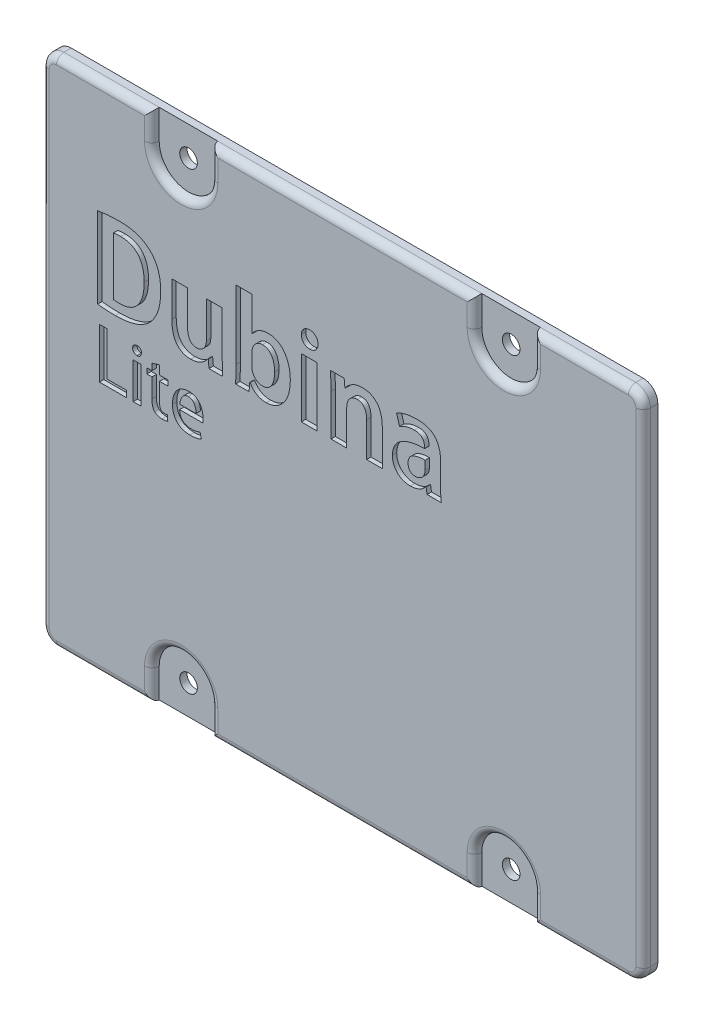
SolidWorks part; units mm, degrees
ref_plane "Спереди" through (0, 0, 0) normal (0, 0, 1) x (1, 0, 0)
ref_plane "Сверху" through (0, 0, 0) normal (0, 1, 0) x (1, 0, 0)
ref_plane "Справа" through (0, 0, 0) normal (1, 0, 0) x (0, 0, -1)
other "Configuration Table"
sketch "Эскиз2" plane through (0, 0, 0) normal (0, 0, 1) x (1, 0, 0)
  line L0 (-39, 35) -> (39, 35)
  line L1 (41, 33) -> (41, -33)
  line L2 (39, -35) -> (-39, -35)
  line L3 (-41, -33) -> (-41, 33)
  line L4 (-18, -31) -> (-18, -35)
  line L5 (-26, -31) -> (-26, -35)
  line L6 (26, -31) -> (26, -35)
  line L7 (18, -31) -> (18, -35)
  line L8 (26, 31) -> (26, 35)
  line L9 (18, 31) -> (18, 35)
  line L10 (-18, 31) -> (-18, 35)
  line L11 (-26, 31) -> (-26, 35)
  arc A0 (-39, 35) -> (-41, 33) centre (-39, 33) ccw construction
  arc A1 (41, 33) -> (39, 35) centre (39, 33) ccw construction
  arc A2 (39, -35) -> (41, -33) centre (39, -33) ccw construction
  arc A3 (-41, -33) -> (-39, -35) centre (-39, -33) ccw construction
  arc A4 (-39, 35) -> (-41, 33) centre (-39, 33) ccw
  arc A5 (41, 33) -> (39, 35) centre (39, 33) ccw
  arc A6 (39, -35) -> (41, -33) centre (39, -33) ccw
  arc A7 (-41, -33) -> (-39, -35) centre (-39, -33) ccw
  circle A8 centre (-22, 31) radius 1.2 construction
  circle A9 centre (22, 31) radius 1.2 construction
  circle A10 centre (22, -31) radius 1.2 construction
  circle A11 centre (-22, -31) radius 1.2 construction
  circle A12 centre (-22, 31) radius 1.2
  circle A13 centre (22, 31) radius 1.2
  circle A14 centre (22, -31) radius 1.2
  circle A15 centre (-22, -31) radius 1.2
  arc A16 (-26, 31) -> (-18, 31) centre (-22, 31) ccw
  arc A17 (18, 31) -> (26, 31) centre (22, 31) ccw
  arc A18 (26, -31) -> (18, -31) centre (22, -31) ccw
  arc A19 (-18, -31) -> (-26, -31) centre (-22, -31) ccw
  circle M9 centre (-22, -31) radius 1.2
  line M10 (-41, -29) -> (-41, -33)
  arc M11 (-41, -33) -> (-39, -35) centre (-39, -33) ccw
  line M12 (-39, -35) -> (-15, -35)
  line M13 (-15, -35) -> (-15, -29)
  line M14 (-15, -29) -> (-10, -20.5)
  line M15 (-10, -20.5) -> (-29, -20.5)
  line M17 (-29, -29) -> (-41, -29)
extrude "Бобышка-Вытянуть1" add sketch "Эскиз2" along normal blind 2 contours A18 L6 L2 A6 L1 A5 L0 L8 A17 L9 L10 A16 L11 A4 L3 L7 M17 M15 M14 M13 | A19 L4 L2 L5 M13 M14 M15 M17 M10 M11 M12 region at (0, 0, 0)
extrude "Бобышка-Вытянуть2" add sketch "Эскиз2<3>" along normal blind 1 contours L4 A19 L5 L2 M9 | L6 A18 L7 L2 A14 | L9 A17 L8 L0 A13 | L11 A16 L10 L0 A12 region at (-22, 34.8869, 0) region at (22, 34.8869, 0) region at (-25.8869, -33, 0) region at (18.1131, -33, 0)
sketch "Эскиз2<3>" plane through (0, 0, 0) normal (0, 0, 1) x (1, 0, 0) same geometry as "Эскиз2"
fillet "Скругление1" radius 1 24 edges at (-40.4142, 34.4142, 2) (-32.5, 35, 2) (-26, 33, 2) (-22, 27, 2) (-18, 33, 2) (0, 35, 2) (18, 33, 2) (22, 27, 2) (26, 33, 2) (32.5, 35, 2) (40.4142, 34.4142, 2) (41, 0, 2) (40.4142, -34.4142, 2) (32.5, -35, 2) (26, -33, 2) (22, -27, 2) (18, -33, 2) (0, -35, 2) (-18, -33, 2) (-22, -27, 2) (-26, -33, 2) (-32.5, -35, 2) (-40.4142, -34.4142, 2) (-41, 0, 2)
sketch "Эскиз3" plane through (0, 0, 2) normal (0, 0, 1) x (1, 0, 0)
  text T0 "Dubina" font "Adobe Gothic Std B" height in points 36
  text T1 "Lite" font "Adobe Heiti Std R" height in points 22
extrude "Вырез-Вытянуть1" cut sketch "Эскиз3" against normal blind 0.6
